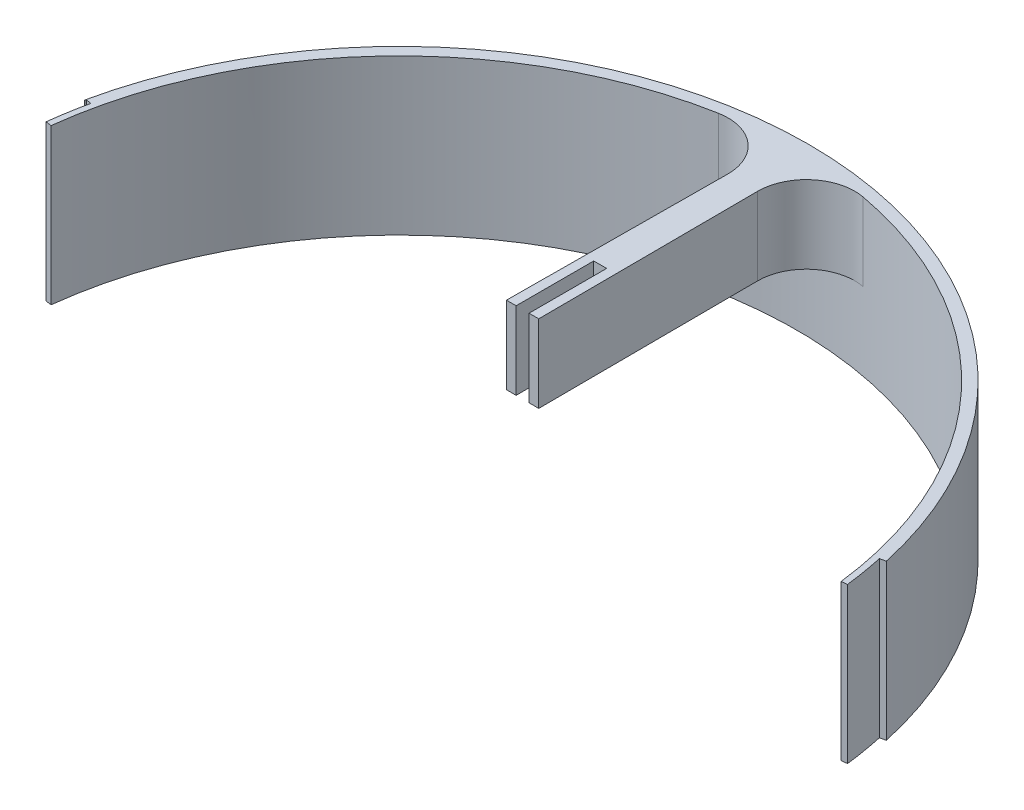
SolidWorks part; units mm, degrees
ref_plane "Plan de face" through (0, 0, 0) normal (0, 0, 1) x (1, 0, 0)
ref_plane "Plan de dessus" through (0, 0, 0) normal (0, 1, 0) x (1, 0, 0)
ref_plane "Plan de droite" through (0, 0, 0) normal (1, 0, 0) x (0, 0, -1)
sketch "Esquisse2" plane through (0, 0, 0) normal (0, 1, 0) x (1, 0, 0)
  circle A0 centre (0, 0) radius 105.5
  dimension "D1" = 211
extrude "Boss.-Extru.1" add sketch "Esquisse2" along normal blind 20
sketch "Esquisse3" plane through (0, 20, 0) normal (0, 1, 0) x (1, 0, 0)
  line L0 (0, 0) -> (0, -37.8201) construction
  line L1 (-22.2901, -5) -> (26.3096, -5) construction
  line L3 (-25.4411, -19.4651) -> (-74.7068, -47.4761)
  line L4 (25.4084, -19.5127) -> (74.6164, -47.6194)
  arc A0 (-78.0463, -66.4457) -> (77.919, -66.5949) centre (0, 0) ccw
  circle A1 centre (0, 0) radius 105.5 construction
  arc A2 (-74.7068, -47.4761) -> (-78.0463, -66.4457) centre (-68.5285, -58.3425) ccw
  arc A3 (77.919, -66.5949) -> (74.6164, -47.6194) centre (68.4167, -58.4736) ccw
  arc A5 (-7.7779, -18.4256) -> (7.7444, -18.4397) centre (0, 0) ccw
  arc A7 (-25.4411, -19.4651) -> (-7.7779, -18.4256) centre (-15.5558, -36.8513) cw
  arc A8 (7.7444, -18.4397) -> (25.4084, -19.5127) centre (15.4889, -36.8795) cw
  point P16 (0, -5)
  dimension "D3" = 102.5
  dimension "D6" = 25
  dimension "D2" = 25
  dimension "D5" = 20
  dimension "D7" = 20
  dimension "D1" = 5
extrude "Enlèv. mat.-Extru.1" cut sketch "Esquisse3" against normal through all
pattern_circular "Répétition circulaire1" count 3 over 360 about axis through (0, 20, 0) along (0, 1, 0) of "Enlèv. mat.-Extru.1"
sketch "Esquisse4" plane through (0, 20, 0) normal (0, 1, 0) x (1, 0, 0)
  circle A0 centre (-16.5, 0) radius 1.5
  circle A1 centre (16.5, 0) radius 1.5
  circle A2 centre (0, 16.5) radius 1.5
  circle A3 centre (0, -16.5) radius 1.5
  dimension "D1" = 3
  dimension "D2" = 3
  dimension "D5" = 3
  dimension "D6" = 3
  dimension "D3" = 16.5
  dimension "D4" = 16.5
  dimension "D7" = 16.5
  dimension "D8" = 16.5
extrude "Enlèv. mat.-Extru.2" cut sketch "Esquisse4" against normal through all
sketch "Esquisse5" plane through (0, 20, 0) normal (0, 1, 0) x (1, 0, 0)
  circle A0 centre (0, 0) radius 13
  dimension "D1" = 26
extrude "Enlèv. mat.-Extru.3" cut sketch "Esquisse5" against normal blind 3
sketch "Esquisse6" plane through (0, 17, 0) normal (0, 1, 0) x (1, 0, 0)
  circle A0 centre (0, 0) radius 14
extrude "Enlèv. mat.-Extru.4" cut sketch "Esquisse6" against normal through all
sketch "Esquisse7" plane through (0, 20, 0) normal (0, 1, 0) x (1, 0, 0)
  line L0 (-16.5, 0) -> (0, -16.5) construction
  line L1 (-73.3003, -42.3791) -> (-18.5313, -10.4184) construction
  line L2 (-78.5478, -40.81) -> (-29.6027, -12.2479) construction
  line L3 (-24.4395, -2.3515) -> (-11.5191, -24.4923) construction
  line L4 (-22.6547, -9.9301) -> (-17.499, -6.9215) construction
  line L5 (-14.9362, -11.215) -> (-21.6686, -15.1437) construction
  line L6 (-78.7767, -48.7003) -> (-18.5358, -13.5465)
  line L7 (-78.7767, -48.7003) -> (-81.4978, -44.0373)
  line L9 (-81.4978, -44.0373) -> (-21.257, -8.8835)
  line L10 (-78.7767, -48.7003) -> (-21.257, -8.8835) construction
  line L11 (-18.5358, -13.5465) -> (-81.4978, -44.0373) construction
  line L12 (-8.25, -8.25) -> (-5.2218, -5.2218) construction
  line L13 (-11.0784, -5.4216) -> (-9.3631, -3.7063) construction
  line L14 (-5.4216, -11.0784) -> (-2.758, -8.4149) construction
  line L15 (-12.4833, -2.3515) -> (-2.758, -12.7041)
  line L16 (-12.4833, -2.3515) -> (-12.7856, -2.3515)
  circle A0 centre (0, 0) radius 13 construction
  arc A1 (-21.257, -8.8835) -> (-12.7856, -2.3515) centre (-42.2756, 27.1348) ccw
  arc A2 (-18.5358, -13.5465) -> (-2.758, -12.7041) centre (-9.8276, -28.4693) cw
  point P14 (-47.6812, -27.4289)
  point P16 (-50.0168, -28.7919)
  dimension "D1" = 4
  dimension "D2" = 2.5
  dimension "D3" = 2.5
  dimension "D4" = 4
  dimension "D5" = 4
extrude "Enlèv. mat.-Extru.5" cut sketch "Esquisse7" against normal blind 5
sketch "Esquisse9" plane through (0, 0, 0) normal (0, -1, 0) x (1, 0, 0)
  line L0 (-117.3657, 7.7167) -> (-111.3657, 18.109)
  line L1 (0, 0) -> (-127.9608, 73.8782) construction
  line L2 (-131.1472, 15.6735) -> (-96.8675, -4.118) construction
  line L4 (-111.3657, 18.109) -> (-107.9016, 16.109)
  line L5 (-107.3657, 25.0372) -> (-103.9016, 23.0372)
  line L6 (-107.9016, 16.109) -> (-103.9016, 23.0372)
  line L7 (-107.3657, 25.0372) -> (-91.3657, 52.75)
  circle A0 centre (0, 0) radius 105.5 construction
  arc A1 (-104.8789, -11.4306) -> (-117.3657, 7.7167) centre (-130.0012, -14.1687) ccw
  arc A2 (-91.3657, 52.75) -> (-104.8789, -11.4306) centre (0, 0) ccw
  point P4 (-91.3657, 52.75)
  point P9 (-117.3657, 7.7167)
  dimension "D3" = 32
  dimension "D2" = 0
  dimension "D4" = 8
  dimension "D5" = 4
  dimension "D6" = 52.75
extrude "Boss.-Extru.4" add sketch "Esquisse9" against normal blind 20
sketch "Esquisse11" plane through (-91.3657, 0, 52.75) normal (-0.866, 0, 0.5) x (0.5, 0, 0.866)
  line L0 (-40, 0) -> (-52, 0) construction
  line L1 (-50, 5) -> (-42, 5)
  line L2 (-50, 5) -> (-50, 13)
  line L3 (-50, 13) -> (-42, 13)
  line L4 (-42, 5) -> (-42, 13)
  line L6 (-52, 20) -> (-52, 0) construction
  dimension "D1" = 8
  dimension "D2" = 8
  dimension "D3" = 5
  dimension "D4" = 2
extrude "Enlèv. mat.-Extru.6" cut sketch "Esquisse11" against normal blind 20
sketch "Esquisse12" plane through (-91.3657, 0, 52.75) normal (-0.866, 0, 0.5) x (0.5, 0, 0.866)
  line L0 (-40, 20) -> (-40, 0) construction
  line L1 (-50.7054, 3.9045) -> (-40, 3.9045)
  line L2 (-50.7054, 3.9045) -> (-50.7054, 16.1116)
  line L3 (-50.7054, 16.1116) -> (-40, 16.1116)
  line L4 (-40, 3.9045) -> (-40, 16.1116)
extrude "Boss.-Extru.5" add sketch "Esquisse12" against normal blind 5
sketch "Esquisse13" plane through (-87.0356, 0, 50.25) normal (0.866, 0, -0.5) x (-0.5, 0, -0.866)
  line L0 (50, 5) -> (42, 5) construction
  line L2 (42, 5) -> (42, 13) construction
  circle A0 centre (46, 9) radius 1.5
  point P7 (42, 10.6595)
  point P8 (44.4531, 9.3264)
  dimension "D1" = 3
  dimension "D2" = 4
  dimension "D3" = 4
extrude "Enlèv. mat.-Extru.7" cut sketch "Esquisse13" against normal through all
sketch "Esquisse22" plane through (0, 20, 0) normal (0, 1, 0) x (1, 0, 0)
  line L0 (-91.3657, -52.75) -> (-78.8757, -74.3833)
  line L1 (-78.8757, -74.3833) -> (-76.2776, -72.8833)
  line L2 (-76.2776, -72.8833) -> (-70.2776, -83.2756)
  line L3 (-58.7776, -103.1942) -> (-45.1731, -95.3396)
  line L4 (-75.8355, -73.3432) -> (-78.0603, -67.6298)
  line L5 (-78.0603, -67.6298) -> (-81.7873, -66.6415)
  line L9 (-68.7776, -85.8737) -> (-58.7776, -103.1942)
  line L10 (-70.2776, -83.2756) -> (-68.7776, -85.8737)
  arc A0 (-91.3657, -52.75) -> (-104.8789, 11.4306) centre (0, 0) ccw construction
  arc A1 (-91.3657, -52.75) -> (-81.7873, -66.6415) centre (0, 0) ccw
  arc A5 (-75.8355, -73.3432) -> (-45.1731, -95.3396) centre (0, 0) ccw
  point P6 (-76.2776, -72.8833)
  dimension "D1" = 3
  dimension "D2" = 35
extrude "Boss.-Extru.11" add sketch "Esquisse22" against normal blind 20
sketch "Esquisse25" plane through (-88.7676, 0, 51.25) normal (-0.866, 0, 0.5) x (0.5, 0, 0.866)
  line L0 (59.98, 0) -> (59.98, 20) construction
  line L1 (49.98, 6) -> (57.98, 6)
  line L2 (49.98, 6) -> (49.98, 14)
  line L3 (49.98, 14) -> (57.98, 14)
  line L4 (57.98, 6) -> (57.98, 14)
  line L5 (24.98, 20) -> (59.98, 20) construction
  dimension "D1" = 2
  dimension "D2" = 8
  dimension "D3" = 8
  dimension "D4" = 6
extrude "Enlèv. mat.-Extru.21" cut sketch "Esquisse25" against normal blind 20
sketch "Esquisse26" plane through (-88.7676, 0, 51.25) normal (-0.866, 0, 0.5) x (0.5, 0, 0.866)
  line L1 (49.98, 6) -> (57.98, 6)
  line L2 (49.98, 6) -> (49.98, 14)
  line L3 (49.98, 14) -> (57.98, 14)
  line L4 (57.98, 6) -> (57.98, 14)
extrude "Boss.-Extru.12" add sketch "Esquisse26" against normal blind 4
sketch "Esquisse28" plane through (-85.3035, 0, 49.25) normal (0.866, 0, -0.5) x (-0.5, 0, -0.866)
  line L0 (-49.98, 14) -> (-49.98, 6) construction
  line L1 (-49.98, 6) -> (-57.98, 6) construction
  circle A0 centre (-53.98, 10) radius 1.5
  dimension "D1" = 3
  dimension "D2" = 4
  dimension "D3" = 4
extrude "Enlèv. mat.-Extru.22" cut sketch "Esquisse28" against normal through all
sketch "Esquisse29" plane through (-88.7676, 0, 51.25) normal (-0.866, 0, 0.5) x (0.5, 0, 0.866)
  line L0 (24.98, 0) -> (59.98, 0) construction
  line L1 (44.98, 0) -> (48.98, 0)
  line L2 (44.98, 0) -> (44.98, 20)
  line L3 (44.98, 20) -> (48.98, 20)
  line L4 (48.98, 0) -> (48.98, 20)
  line L5 (24.98, 20) -> (59.98, 20) construction
  line L7 (59.98, 0) -> (59.98, 20) construction
  dimension "D1" = 4
  dimension "D2" = 11
extrude "Enlèv. mat.-Extru.23" cut sketch "Esquisse29" against normal blind 4
sketch "Esquisse30" plane through (-88.7676, 0, 51.25) normal (-0.866, 0, 0.5) x (0.5, 0, 0.866)
  line L0 (44.98, 20) -> (44.98, 0) construction
  line L1 (41.98, 6) -> (33.98, 6)
  line L2 (41.98, 6) -> (41.98, 14)
  line L3 (41.98, 14) -> (33.98, 14)
  line L4 (33.98, 6) -> (33.98, 14)
  line L5 (24.98, 20) -> (44.98, 20) construction
  dimension "D1" = 3
  dimension "D2" = 8
  dimension "D3" = 8
  dimension "D4" = 6
extrude "Enlèv. mat.-Extru.24" cut sketch "Esquisse30" against normal blind 23
sketch "Esquisse31" plane through (-88.7676, 0, 51.25) normal (-0.866, 0, 0.5) x (0.5, 0, 0.866)
  line L1 (33.98, 6) -> (41.98, 6)
  line L2 (33.98, 6) -> (33.98, 14)
  line L3 (33.98, 14) -> (41.98, 14)
  line L4 (41.98, 6) -> (41.98, 14)
extrude "Boss.-Extru.13" add sketch "Esquisse31" against normal blind 2
sketch "Esquisse32" plane through (-87.0356, 0, 50.25) normal (0.866, 0, -0.5) x (-0.5, 0, -0.866)
  line L0 (-33.98, 6) -> (-41.98, 6) construction
  line L1 (-33.98, 14) -> (-33.98, 6) construction
  circle A0 centre (-37.98, 10) radius 1.5
  dimension "D1" = 3
  dimension "D2" = 4
  dimension "D3" = 4
extrude "Enlèv. mat.-Extru.25" cut sketch "Esquisse32" against normal blind 22
sketch "Esquisse33" plane through (12.49, 0, 21.6333) normal (0.5, 0, 0.866) x (0.866, 0, -0.5)
  line L1 (-105.5, 20) -> (-102.5, 20)
  line L2 (-105.5, 20) -> (-105.5, 0)
  line L3 (-105.5, 0) -> (-102.5, 0)
  line L4 (-102.5, 20) -> (-102.5, 0)
extrude "Boss.-Extru.14" add sketch "Esquisse33" along normal blind 5
mirror "Symétrie1" about plane through (0, 0, 0) normal (1, 0, 0) of "Enlèv. mat.-Extru.25", "Boss.-Extru.13", "Enlèv. mat.-Extru.24", "Enlèv. mat.-Extru.22", "Boss.-Extru.12", "Enlèv. mat.-Extru.21", "Boss.-Extru.5", "Enlèv. mat.-Extru.6", "Boss.-Extru.4", "Enlèv. mat.-Extru.7", "Boss.-Extru.11", "Enlèv. mat.-Extru.23", "Boss.-Extru.14"
sketch "Esquisse20" plane through (-87.9016, 0, 50.75) normal (-0.866, 0, 0.5) x (0.5, 0, 0.866)
  line L0 (-32, 20) -> (-40, 20) construction
  line L1 (-40, 0) -> (-36, 0)
  line L2 (-40, 0) -> (-40, 20)
  line L3 (-40, 20) -> (-36, 20)
  line L4 (-36, 0) -> (-36, 20)
extrude "Boss.-Extru.9" add sketch "Esquisse20" along normal blind 8
sketch "Esquisse21" plane through (87.9016, 0, 50.75) normal (0.866, 0, 0.5) x (0.5, 0, -0.866)
  line L0 (32, 0) -> (40, 0) construction
  line L1 (32, 20) -> (36, 20)
  line L2 (32, 20) -> (32, 0)
  line L3 (32, 0) -> (36, 0)
  line L4 (36, 20) -> (36, 0)
extrude "Boss.-Extru.10" add sketch "Esquisse21" along normal blind 8
sketch "Esquisse36" plane through (0, 0, 0) normal (0, -1, 0) x (1, 0, 0)
  circle A0 centre (0, 0) radius 105.5
  circle A1 centre (0, 0) radius 102.5
extrude "Boss.-Extru.16" add sketch "Esquisse36" along normal blind 20 contours A1 | A0
sketch "Esquisse37" plane through (0, 20, 0) normal (0, 1, 0) x (1, 0, 0)
  line L0 (-78.9735, -48.8139) -> (-78.7767, -48.7003)
  line L1 (-76.3757, -78.7134) -> (-107.3657, -25.0372) construction
  line L3 (-82.6337, -62.4742) -> (-74.0374, -77.3634)
  line L4 (-74.0374, -77.3634) -> (-76.3757, -78.7134)
  line L5 (-76.3757, -78.7134) -> (-89.3273, -56.2805)
  line L9 (-78.7767, -48.7003) -> (-81.4978, -44.0373)
  line L10 (-73.7776, -77.2134) -> (-76.3757, -78.7134) construction
  arc A0 (-82.6337, -62.4742) -> (-78.9735, -48.8139) centre (-73.9735, -57.4742) cw
  arc A1 (-81.4978, -44.0373) -> (-89.3273, -56.2805) centre (-73.9735, -57.4742) ccw
  dimension "D2" = 10
  dimension "D1" = 2.7
  dimension "D3" = 0
extrude "Enlèv. mat.-Extru.26" cut sketch "Esquisse37" against normal blind 5
sketch "Esquisse38" plane through (0, 20, 0) normal (0, 1, 0) x (-1, 0, 0)
  line L0 (-78.8757, 74.3833) -> (-76.3757, 78.7134)
  line L2 (-82.6324, 62.4765) -> (-76.5374, 73.0333)
  line L4 (-78.8757, 74.3833) -> (-89.3259, 56.2831)
  line L5 (-73.7776, 77.2134) -> (-76.3757, 78.7134) construction
  line L6 (-76.5374, 73.0333) -> (-74.0374, 77.3634)
  line L7 (-74.0374, 77.3634) -> (-76.3757, 78.7134)
  arc A0 (-89.3259, 56.2831) -> (-82.6324, 62.4765) centre (-95.9692, 70.1765) ccw
  point P8 (-95.9692, 70.1765)
  dimension "D1" = 2.7
  dimension "D4" = 15.4
extrude "Enlèv. mat.-Extru.27" cut sketch "Esquisse38" against normal blind 5
fillet "Congé2" radius 2.5 5 edges at (-13.6071, 15, 11.6099) (-48.6563, 15, 31.1234) (-78.8751, 15, 48.7571) (-83.6327, 15, 54.886) (-78.3356, 15, 69.9188)
fillet "Congé4" radius 2.5 3 edges at (-51.3774, 15, 26.4604) (-17.2825, 15, 6.2485) (-86.9476, 15, 49.1773)
fillet "Congé5" radius 2.5 2 edges at (78.3349, 15, 69.9199) (85.5102, 15, 58.873)
sketch "Esquisse39" plane through (0, 20, 0) normal (0, 1, 0) x (1, 0, 0)
  line L0 (-101.7887, 12.0544) -> (-4.1367, 31.7652)
  line L1 (1.6943, 31.762) -> (1.6943, 51.762)
  line L2 (1.6943, 51.762) -> (-1.6367, 51.762)
  line L3 (-1.6367, 51.762) -> (-1.6367, 31.7638)
  line L4 (4.1943, 31.7607) -> (1.6943, 31.762)
  line L6 (-4.1367, 31.7652) -> (-1.6367, 31.7638)
  line L7 (101.6442, 12.0838) -> (4.1943, 31.7607)
  line L8 (101.6442, 12.0838) -> (103.2728, 12.2774)
  line L9 (-101.6262, 22.0934) -> (-102.978, 22.3872)
  line L10 (-101.7887, 12.0544) -> (-103.2783, 12.2308)
  line L11 (-102.978, 22.3872) -> (-207.574, -147.5567)
  line L12 (101.6162, 22.1392) -> (103.0818, 22.4586)
  line L13 (-207.574, -147.5567) -> (216.7222, -147.5567)
  line L14 (216.7222, -147.5567) -> (103.0818, 22.4586)
  arc A0 (104.8789, 11.4306) -> (-104.8789, 11.4306) centre (0, 0) ccw construction
  arc A1 (103.2728, 12.2774) -> (101.6162, 22.1392) centre (0, 0) ccw
  arc A2 (-18.5205, 100.8129) -> (-96.6324, -34.1824) centre (0, 0) ccw construction
  arc A3 (-101.6262, 22.0934) -> (-103.2783, 12.2308) centre (0, 0) ccw
  point P4 (101.6162, 22.1392)
  point P8 (101.6442, 12.0838)
  point P10 (-101.7887, 12.0544)
  point P17 (-101.6262, 22.0934)
  point P19 (103.2728, 12.2774)
  point P20 (103.0818, 22.4586)
  point P31 (-103.2783, 12.2308)
  dimension "D4" = 1.5
  dimension "D1" = 2.5
  dimension "D2" = 2.5
  dimension "D3" = 20
  dimension "D5" = 10
  dimension "D6" = 10
extrude "Enlèv. mat.-Extru.29" cut sketch "Esquisse39" against normal through all
